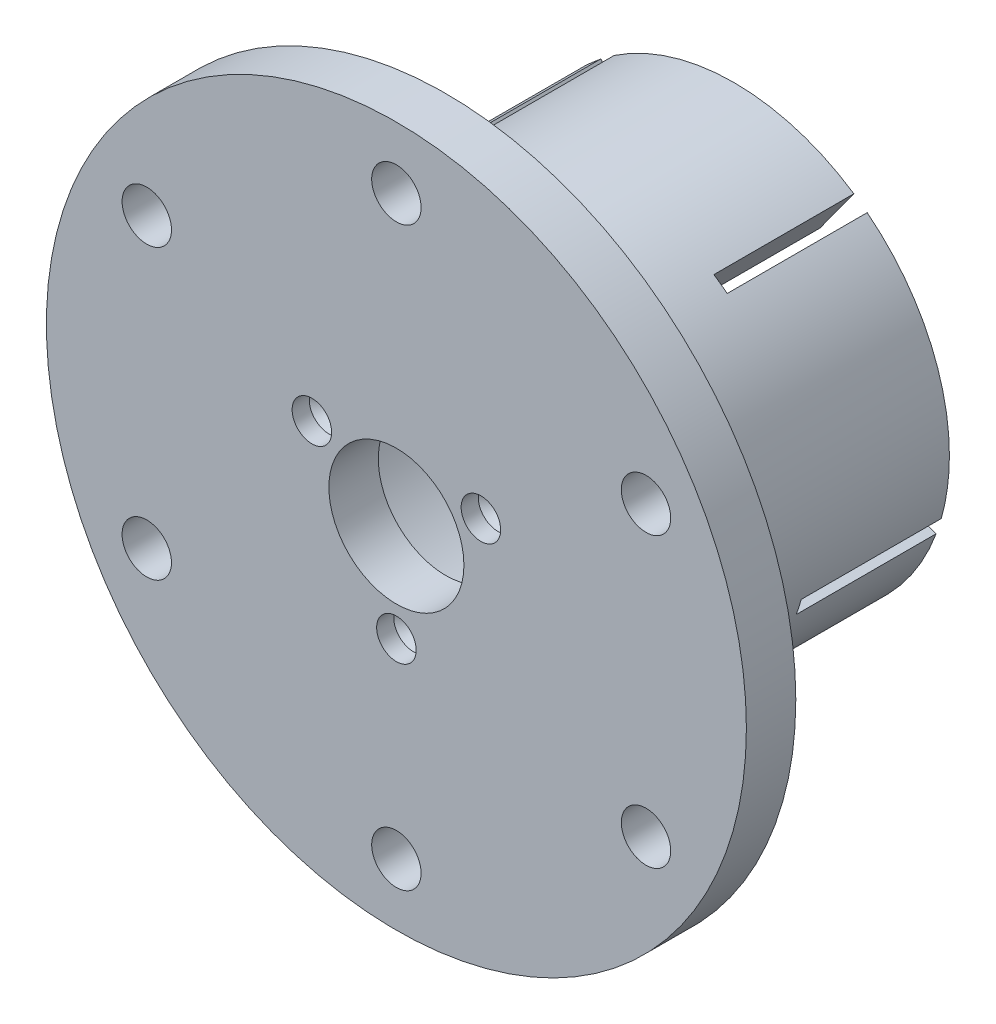
SolidWorks part; units mm, degrees
ref_plane "Front Plane" through (0, 0, 0) normal (0, 0, 1) x (1, 0, 0)
ref_plane "Top Plane" through (0, 0, 0) normal (0, 1, 0) x (1, 0, 0)
ref_plane "Right Plane" through (0, 0, 0) normal (1, 0, 0) x (0, 0, -1)
sketch "Sketch1" plane through (0, 0, 0) normal (0, 0, 1) x (1, 0, 0)
  line L1 (-2.9, 18.9291) -> (2.9, 18.9291) construction
  line L2 (-2.9, 18.9291) -> (-2.9, 16.7508)
  line L4 (2.9, 18.9291) -> (2.9, 16.7508)
  circle A0 centre (0, 0) radius 19.15
  circle A1 centre (0, 0) radius 17
  circle A2 centre (0, 0) radius 26.15
  point P7 (0, 17)
  point P13 (0, 18.9291)
  dimension "D1" = 38.3
  dimension "D3" = 34
  dimension "D4" = 7
  dimension "D2" = 5.8
extrude "Boss-Extrude1" add sketch "Sketch1" against normal blind 35 contours A2 A0 | L1 L2 A1 L4 | A0 L1 region at (0, 19.0175, 0) region at (0, 17.9218, 0) region at (-25.4104, 0, 0)
fillet "Fillet1" radius 0.7 2 edges at (2.9, 18.9291, -17.5) (-2.9, 18.9291, -17.5)
sketch "Sketch2" plane through (0, 0, 0) normal (0, 0, 1) x (1, 0, 0)
  line L0 (0, -8.2) -> (0, -15.5) construction
  circle A0 centre (0, 35) radius 3
  circle A1 centre (30.3109, 17.5) radius 3
  circle A2 centre (30.3109, -17.5) radius 3
  circle A3 centre (0, -35) radius 3
  circle A4 centre (-30.3109, -17.5) radius 3
  circle A5 centre (-30.3109, 17.5) radius 3
  circle A6 centre (0, 0) radius 42.5
  circle A7 centre (0, 0) radius 8.2
  circle A8 centre (0, 0) radius 17 construction
  circle A10 centre (0, 0) radius 17
  circle A11 centre (0, -11.85) radius 1.35
  circle A13 centre (-10.2624, 5.925) radius 1.35
  circle A14 centre (10.2624, 5.925) radius 1.35
  point P15 (0, 0)
  point P34 (0, 0)
  dimension "D2" = 6
  dimension "D4" = 85
  dimension "D5" = 16.4
  dimension "D6" = 2.7
  dimension "D1" = 35
  dimension "D9" = 15.5
  dimension "D3" = 6
  dimension "D7" = 3
extrude "Boss-Extrude2" add sketch "Sketch2" along normal blind 6 contours A6 A10 A0 A1 A2 A3 A4 A5 | A10 A7 region at (-41.2979, 0, 0) region at (-16.5192, 0, 0)
sketch "Sketch3" plane through (0, 0, -35) normal (0, 0, -1) x (-1, 0, 0)
  line L1 (-1, -27.5229) -> (1, -27.5229)
  line L2 (0, 0) -> (0, -27.5229) construction
  line L3 (-1, -27.5229) -> (-1, 0)
  line L4 (-1, 0) -> (1, 0)
  line L5 (1, -27.5229) -> (1, 0)
  dimension "D1" = 2
extrude "Cut-Extrude1" cut sketch "Sketch3" against normal blind 17
pattern_circular "CirPattern1" count 5 over 360 about axis through (0, 0, -35) along (0, 0, 1) of "Cut-Extrude1"
chamfer "Chamfer1" distance 8 angle 45 1 edges at (26.15, 0, 0)
sketch "Sketch4" plane through (0, 0, 0) normal (0, 0, -1) x (-1, 0, 0)
  circle A0 centre (0, 35) radius 8
  circle A1 centre (30.3109, 17.5) radius 8
  circle A2 centre (30.3109, -17.5) radius 8
  circle A3 centre (0, -35) radius 8
  circle A4 centre (-30.3109, -17.5) radius 8
  circle A5 centre (-30.3109, 17.5) radius 8
  point P15 (0, 0)
  dimension "D1" = 16
  dimension "D2" = 6
extrude "Cut-Extrude2" cut sketch "Sketch4" along normal through all
sketch "Sketch6" plane through (0, 0, 6) normal (0, 0, 1) x (1, 0, 0)
  circle A0 centre (-10.2624, 5.925) radius 4
  dimension "D1" = 8
sketch "Sketch7" plane through (0, 0, 6) normal (0, 0, 1) x (1, 0, 0)
  circle A0 centre (-10.2624, 5.925) radius 2.4
  circle A1 centre (10.2624, 5.925) radius 2.4
  circle A2 centre (0, -11.85) radius 2.4
  dimension "D1" = 4.8
extrude "Cut-Extrude3" cut sketch "Sketch7" against normal offset from surface (3 mm away) 3 up to face at (1.35, -11.85, 0)
chamfer "Chamfer2" distance 1.1 angle 40 3 edges at (-7.8624, 5.925, 3) (2.4, -11.85, 3) (12.6624, 5.925, 3) first distance on face at (-8.9124, 5.925, 3) first distance on face at (1.35, -11.85, 3) first distance on face at (11.6124, 5.925, 3)
